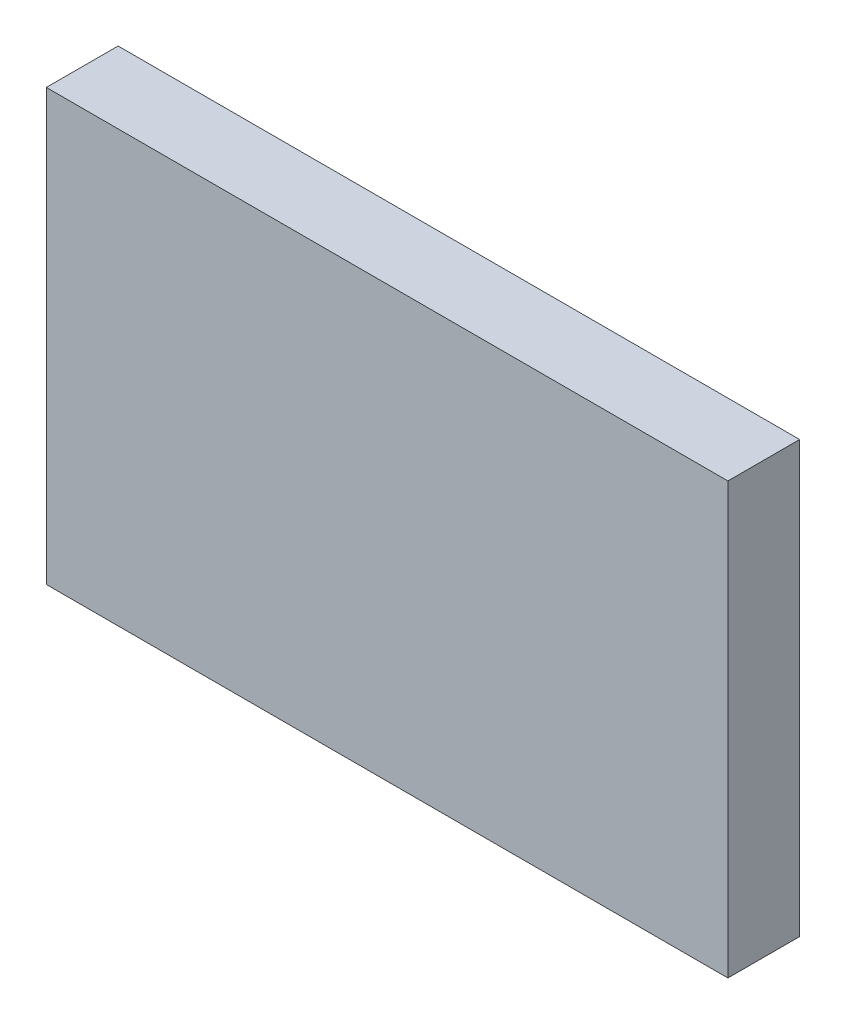
SolidWorks part; units mm, degrees
ref_plane "Front Plane" through (0, 0, 0) normal (0, 0, 1) x (1, 0, 0)
ref_plane "Top Plane" through (0, 0, 0) normal (0, 1, 0) x (1, 0, 0)
ref_plane "Right Plane" through (0, 0, 0) normal (1, 0, 0) x (0, 0, -1)
sketch "Sketch1" plane through (0, 0, 0) normal (0, 0, 1) x (1, 0, 0)
  line L1 (-60.325, -38.1) -> (60.325, -38.1)
  line L2 (-60.325, -38.1) -> (-60.325, 38.1)
  line L3 (-60.325, 38.1) -> (60.325, 38.1)
  line L4 (60.325, -38.1) -> (60.325, 38.1)
  line L5 (-60.325, -38.1) -> (60.325, 38.1) construction
  line L6 (-60.325, 38.1) -> (60.325, -38.1) construction
  point P0 (0, 0)
  dimension "D1" = 76.2
  dimension "D2" = 120.65
extrude "Boss-Extrude1" add sketch "Sketch1" along normal blind 12.7
